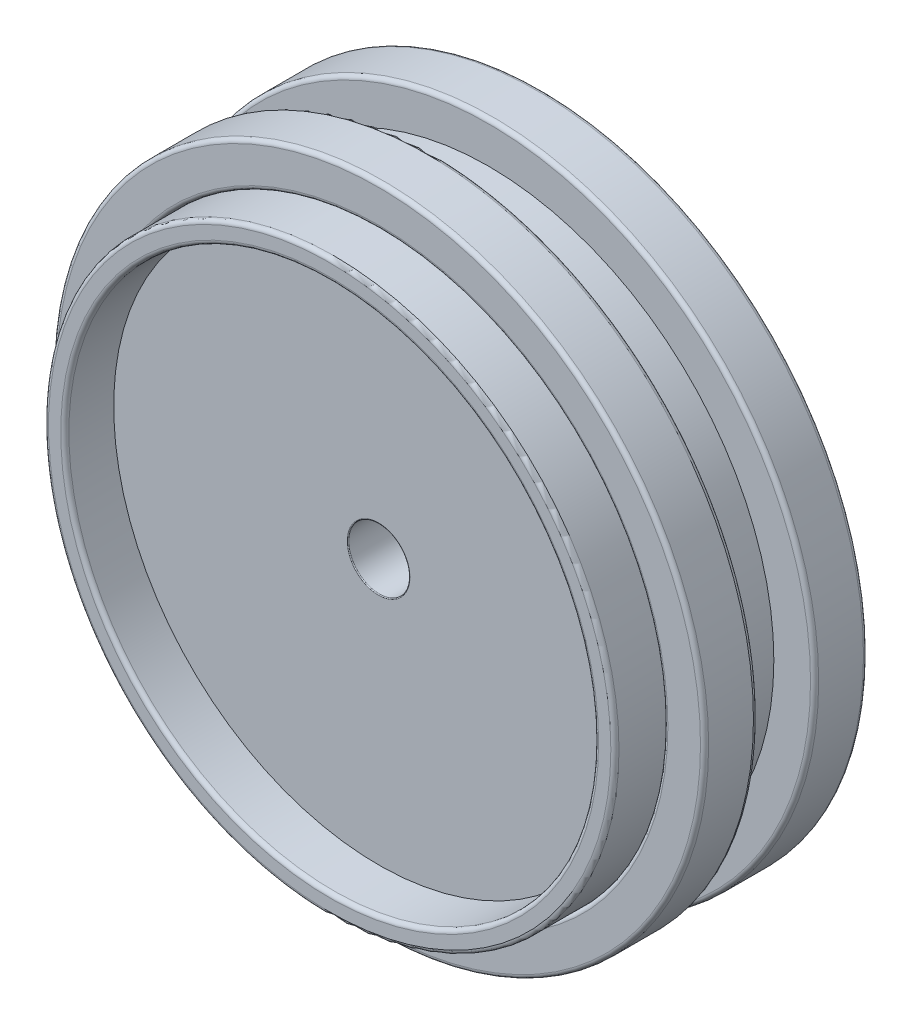
SolidWorks part; units mm, degrees
material "AISI 1020"
ref_plane "Front Plane" through (0, 0, 0) normal (0, 0, 1) x (1, 0, 0)
ref_plane "Top Plane" through (0, 0, 0) normal (0, 1, 0) x (1, 0, 0)
ref_plane "Right Plane" through (0, 0, 0) normal (1, 0, 0) x (0, 0, -1)
sketch "Sketch1" plane through (0, 0, 0) normal (0, 0, 1) x (1, 0, 0)
  circle A0 centre (0, 0) radius 82.55
  circle A1 centre (0, 0) radius 88.9
  circle A2 centre (0, 0) radius 101.6
  dimension "D1" = 165.1
  dimension "D2" = 177.8
  dimension "D3" = 203.2
extrude "Boss-Extrude1" add sketch "Sketch1" along normal blind 15.24 and the other way blind 50.8 contours A1 A0 region at (-86.3855, 0, 0)
extrude "Boss-Extrude2" add sketch "Sketch1<3>" against normal blind 50.8 separate body contours A2 A1 region at (-98.7263, 0, 0)
sketch "Sketch1<3>" plane through (0, 0, 0) normal (0, 0, 1) x (1, 0, 0) same geometry as "Sketch1"
extrude "Boss-Extrude3" add sketch "Sketch1<4>" against normal blind 31.75 separate body contours A0 region at (0, 0, 0)
sketch "Sketch1<4>" plane through (0, 0, 0) normal (0, 0, 1) x (1, 0, 0) same geometry as "Sketch1"
sketch "Sketch4" plane through (0, 0, 0) normal (0, 1, 0) x (1, 0, 0)
  line L0 (101.6, 25.4) -> (-112.628, 25.4) construction
  line L1 (101.6, 0) -> (101.6, 50.8) construction
  line L2 (101.6, 34.29) -> (88.9, 34.29)
  line L3 (88.9, 34.29) -> (88.9, 16.51)
  line L4 (88.9, 16.51) -> (101.6, 16.51)
  line L5 (101.6, 16.51) -> (101.6, 34.29)
  line L7 (0, 0) -> (0, -160.0116) construction
  dimension "D1" = 17.78
  dimension "D3" = 12.7
revolve "Cut-Revolve1" cut sketch "Sketch4" angle 360 about L7
sketch "Sketch5" plane through (0, 0, 0) normal (0, 0, 1) x (1, 0, 0)
  circle A0 centre (0, 0) radius 9.525
  dimension "D1" = 19.05
extrude "Cut-Extrude1" cut sketch "Sketch5" against normal blind 44.45
fillet "Fillet1" radius 1.27 3 edges at (88.9, 0, 0) (-101.6, 0, -16.51) (101.6, 0, 0)
fillet "Fillet2" radius 1.27 3 edges at (82.55, 0, -50.8) (82.55, 0, 15.24) (88.9, 0, 15.24)
fillet "Fillet6" radius 1.27 2 edges at (101.6, 0, -50.8) (-101.6, 0, -34.29)
fillet "Fillet9" radius 0.254 2 edges at (9.525, 0, -31.75) (9.525, 0, 0)
